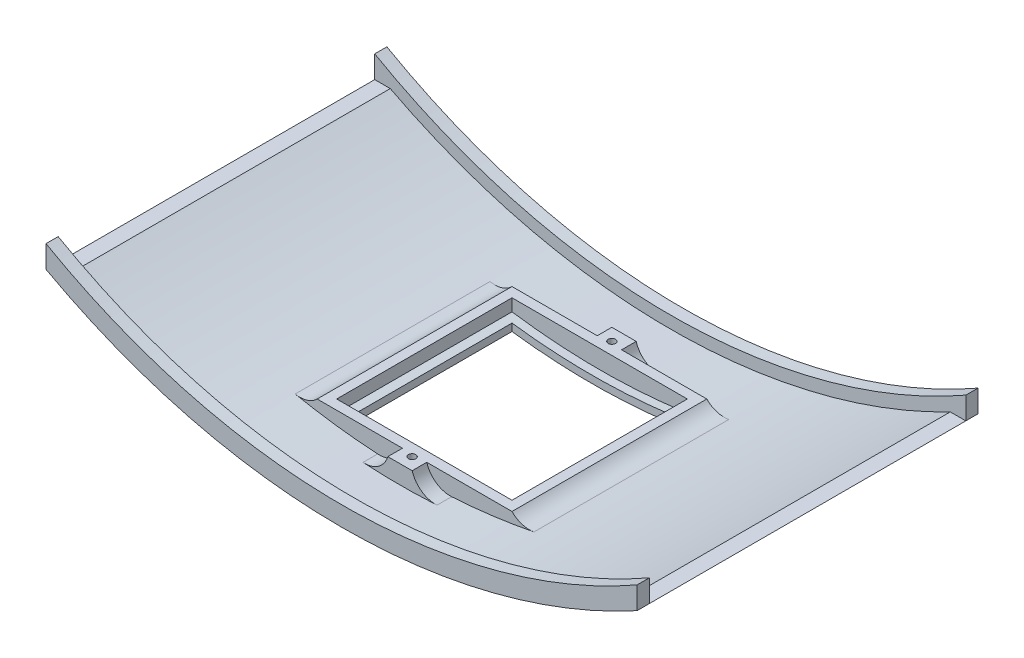
SolidWorks part; units mm, degrees
ref_plane "Piano frontale" through (0, 0, 0) normal (0, 0, 1) x (1, 0, 0)
ref_plane "Piano superiore" through (0, 0, 0) normal (0, 1, 0) x (1, 0, 0)
ref_plane "Piano destro" through (0, 0, 0) normal (1, 0, 0) x (0, 0, -1)
sketch "Schizzo1" plane through (0, 0, 0) normal (0, 0, 1) x (1, 0, 0)
  line L0 (-115, -221.9797) -> (115, -221.9797) construction
  line L1 (0, -221.9797) -> (50000, -221.9797)
  line L2 (-121.3837, -221.9797) -> (-115, -221.9797)
  line L3 (115, -221.9797) -> (121.3837, -221.9797)
  circle A0 centre (0, 0) radius 250
  circle A1 centre (0, 0) radius 253
  point P8 (0, -221.9797)
  dimension "D1" = 500
  dimension "D3" = 506
  dimension "D2" = 230
extrude "Estrusione-Estrusione1" add sketch "Schizzo1" along normal blind 140 contours L1 A1 A0 region at (118.1918, -222.2245, 0)
sketch "Schizzo2" plane through (0, 0, 140) normal (0, 0, 1) x (1, 0, 0)
  line L0 (-121.3837, -221.9797) -> (-121.3837, -218.5543)
  line L1 (121.3837, -221.9797) -> (121.3837, -218.5543)
  line L2 (-121.3837, -218.5543) -> (-121.3837, -212.8168)
  line L3 (121.3837, -218.5543) -> (121.3837, -212.8168)
  circle A0 centre (0, 0) radius 253
  circle A1 centre (0, 0) radius 250
  circle A2 centre (0, 0) radius 245
  line M1 (-115, -221.9797) -> (-121.3837, -221.9797)
  line M3 (121.3837, -221.9797) -> (115, -221.9797)
  arc M4 (115, -221.9797) -> (-115, -221.9797) centre (0, 0) cw
  dimension "D1" = 490
extrude "Estrusione-Estrusione2" add sketch "Schizzo2" against normal blind 5 contours A1 L0 M1 | A2 L2 A1 L3 M4 | A1 L1 M3 region at (-119.2682, -220.8445, 140) region at (-118.9277, -215.6856, 140) region at (119.2682, -220.8445, 140)
sketch "Schizzo3" plane through (0, 0, 0) normal (0, 0, -1) x (-1, 0, 0)
  line L0 (-121.3837, -221.9797) -> (-121.3837, -212.8168)
  line L1 (121.3837, -221.9797) -> (121.3837, -212.8168)
  circle A0 centre (0, 0) radius 253
  circle A1 centre (0, 0) radius 250
  circle A2 centre (0, 0) radius 245
  line M1 (121.3837, -221.9797) -> (115, -221.9797)
  arc M2 (115, -221.9797) -> (-115, -221.9797) centre (0, 0) cw
  line M3 (-115, -221.9797) -> (-121.3837, -221.9797)
  dimension "D1" = 490
extrude "Estrusione-Estrusione3" add sketch "Schizzo3" against normal blind 5 contours A2 L0 A1 L1 M2 | A1 L1 M1 | A1 L0 M3 region at (119.2682, -220.8445, 0) region at (118.9277, -215.6856, 0) region at (-119.2682, -220.8445, 0)
ref_plane "Piano3" through (0, -253, 0) normal (0, -1, 0) x (-1, 0, 0)
sketch "Schizzo4" plane through (0, -253, 0) normal (0, -1, 0) x (-1, 0, 0)
  line L0 (0, 0) -> (0, -50000) construction
  line L1 (121.3837, 0) -> (-121.3837, 0) construction
  line L2 (-121.3837, -70) -> (49878.6163, -70) construction
  line L3 (-121.3837, -135) -> (-121.3837, -5) construction
  line L5 (-32.5, -37.5) -> (32.5, -37.5)
  line L6 (-32.5, -37.5) -> (-32.5, -102.5)
  line L7 (-32.5, -102.5) -> (32.5, -102.5)
  line L8 (32.5, -37.5) -> (32.5, -102.5)
  line L9 (-32.5, -37.5) -> (32.5, -102.5) construction
  line L10 (-32.5, -102.5) -> (32.5, -37.5) construction
  point P4 (0, 0)
  point P9 (-121.3837, -70)
  point P10 (0, -70)
  point P15 (0, 0)
  point P16 (0, 0)
  point P17 (0, -70)
  dimension "D1" = 65
  dimension "D2" = 65
extrude "Taglio-Estrusione1" cut sketch "Schizzo4" against normal through all
sketch "Schizzo6" plane through (0, -253, 0) normal (0, -1, 0) x (-1, 0, 0)
  line L0 (0, 0) -> (0, -50000) construction
  line L1 (-121.3837, -70) -> (49878.6163, -70) construction
  line L2 (-121.3837, -135) -> (-121.3837, -5) construction
  line L3 (-40, -30) -> (40, -30)
  line L4 (-36, -34) -> (36, -34)
  line L5 (-36, -34) -> (-36, -106)
  line L6 (-36, -106) -> (36, -106)
  line L7 (36, -34) -> (36, -106)
  line L8 (-36, -34) -> (36, -106) construction
  line L9 (-36, -106) -> (36, -34) construction
  line L10 (40, -30) -> (40, -110)
  line L11 (-40, -110) -> (40, -110)
  line L12 (-40, -30) -> (-40, -110)
  point P7 (-121.3837, -70)
  point P8 (0, -70)
  dimension "D1" = 72
  dimension "D2" = 72
  dimension "D3" = 4
extrude "Estrusione-Estrusione5" add sketch "Schizzo6" against normal blind 10.61
sketch "Schizzo8" plane through (0, -242.39, 0) normal (0, 1, 0) x (1, 0, 0)
  line L0 (0, -34) -> (0, -50034) construction
  line L1 (-36, -34) -> (36, -34) construction
  line L2 (-36, -70) -> (49964, -70) construction
  line L3 (-36, -34) -> (-36, -106) construction
  line L4 (-5, -24) -> (-5, -30)
  line L5 (-5, -24) -> (5, -24)
  line L6 (-5, -30) -> (5, -30)
  line L7 (5, -24) -> (5, -30)
  line L8 (-5, -24) -> (5, -30) construction
  line L9 (-5, -30) -> (5, -24) construction
  line L10 (-40, -30) -> (40, -30) construction
  line L11 (-5, -110) -> (5, -116) construction
  line L12 (-5, -116) -> (5, -110) construction
  line L13 (5, -116) -> (5, -110)
  line L14 (-5, -110) -> (5, -110)
  line L15 (-5, -116) -> (5, -116)
  line L16 (-5, -116) -> (-5, -110)
  point P4 (0, -34)
  point P9 (-36, -70)
  point P10 (0, 0)
  point P11 (0, -27)
  point P22 (0, -113)
  dimension "D1" = 10
  dimension "D2" = 6
extrude "Estrusione-Estrusione6" add sketch "Schizzo8" against normal blind 8
sketch "Schizzo9" plane through (0, -242.39, 0) normal (0, 1, 0) x (1, 0, 0)
  line L0 (0, 0) -> (0, -50000) construction
  line L1 (5, -24) -> (-5, -24) construction
  line L2 (-5, -29) -> (5, -29) construction
  line L3 (-5, -24) -> (-5, -30) construction
  line L4 (5, -30) -> (5, -24) construction
  line L5 (-5, -111) -> (5, -111) construction
  line L6 (-5, -110) -> (-5, -116) construction
  line L7 (5, -116) -> (5, -110) construction
  line L8 (-5, -116) -> (5, -116) construction
  circle A0 centre (0, -29) radius 1.5
  circle A1 centre (0, -111) radius 1.5
  point P5 (0, -24)
  dimension "D3" = 3
  dimension "D1" = 5
  dimension "D2" = 5
extrude "Taglio-Estrusione2" cut sketch "Schizzo9" against normal blind 5
sketch "Schizzo10" plane through (0, 0, 0) normal (0, 0, -1) x (-1, 0, 0)
  line L0 (-121.3837, -221.9797) -> (-121.3837, -295.1143)
  line L1 (-121.3837, -295.1143) -> (125.3699, -295.1143)
  line L2 (125.3699, -295.1143) -> (121.3837, -221.9797)
  circle A0 centre (0, 0) radius 253
  arc M1 (-121.3837, -221.9797) -> (121.3837, -221.9797) centre (0, 0) ccw
extrude "Taglio-Estrusione3" cut sketch "Schizzo10" against normal through all contours L1 L2 L0 M1 region at (-1.3958, -268.2461, 0)
fillet "Raccordo1" radius 10 6 edges at (5, -249.95, 27) (40, -246.7793, 70) (5, -249.95, 113) (-5, -249.95, 113) (-40, -246.7793, 70) (-5, -249.95, 27)
